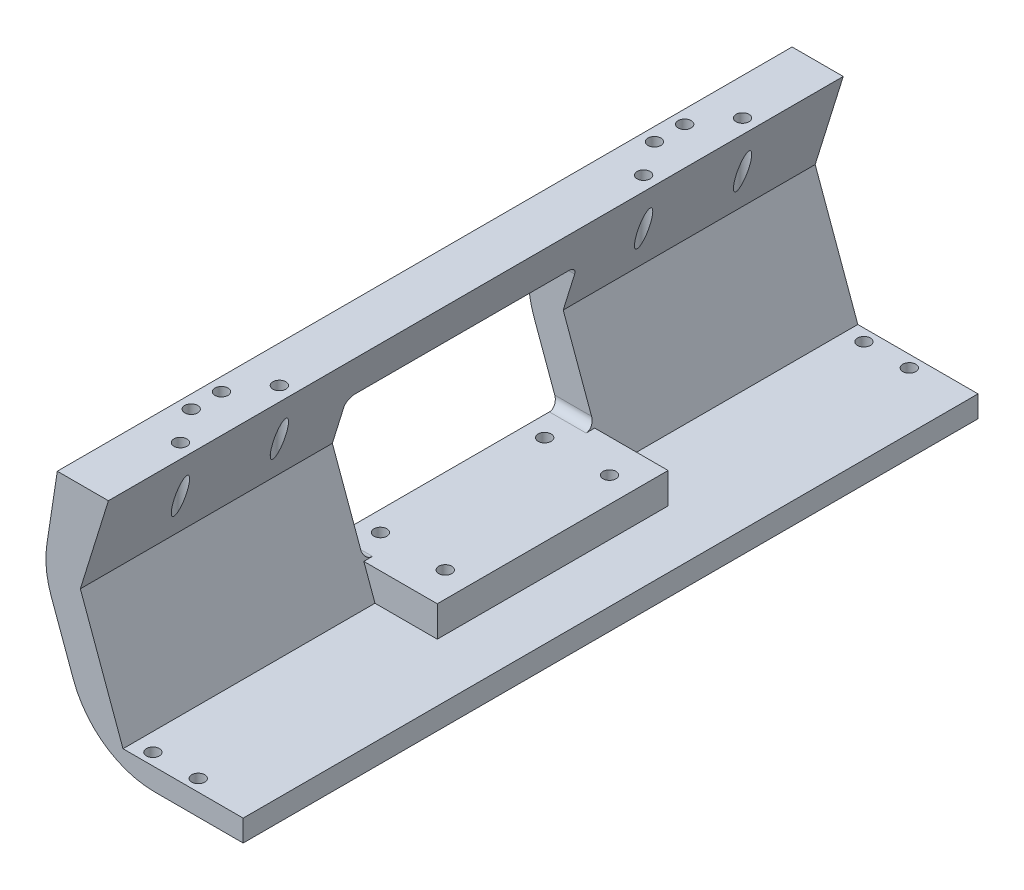
SolidWorks part; units mm, degrees
ref_plane "前视基准面" through (0, 0, 0) normal (0, 0, 1) x (1, 0, 0)
ref_plane "上视基准面" through (0, 0, 0) normal (0, 1, 0) x (1, 0, 0)
ref_plane "右视基准面" through (0, 0, 0) normal (1, 0, 0) x (0, 0, -1)
other "Configuration Table"
sketch "草图1" plane through (0, 0, 0) normal (0, 1, 0) x (1, 0, 0)
  line L0 (77.9817, 90) -> (77.9817, -80)
  line L1 (77.9817, 90) -> (105.7807, 90)
  line L3 (77.9817, -80) -> (105.7807, -80)
  line L4 (105.7807, 90) -> (105.7807, -80)
  circle A0 centre (82.1409, 87.25) radius 1.5
  circle A1 centre (92.6409, 87.25) radius 1.5
  circle A2 centre (82.1409, -77.25) radius 1.5
  circle A3 centre (92.6409, -77.25) radius 1.5
  point P0 (0, 0)
extrude "凸台-拉伸1" add sketch "草图1" along normal blind 5
sketch "草图2" plane through (0, 0, 80) normal (0, 0, 1) x (1, 0, 0)
  line L0 (70.1541, 3.1157) -> (59.6018, 32.1079)
  line L1 (77.9817, 5) -> (68.1152, 32.1079)
  line L2 (77.9817, 5) -> (105.7807, 5) construction
  line L3 (77.9817, 5) -> (63.6209, 44.4558) construction
  line L4 (70.4641, 2.2638) -> (56.1034, 41.7197) construction
  line L5 (70.1541, 3.1157) -> (71.2881, 0)
  line L6 (71.2881, 0) -> (77.9817, 0)
  line L7 (62.7747, 53) -> (74.6027, 53)
  line L9 (77.9817, 5) -> (77.9817, 0)
  line L13 (59.6018, 32.1079) -> (60.4325, 37.5776)
  line L14 (68.1152, 32.1079) -> (74.6027, 53)
  line L17 (62.7721, 53) -> (251.9817, 53) construction
  line L18 (60.4325, 37.5776) -> (62.7747, 53)
  dimension "D1" = 8
  dimension "D2" = 110
extrude "凸台-拉伸2" add sketch "草图2" against normal up to surface (170 mm away) up to face at (91.8812, 2.5, -90)
ref_plane "中间面" through (0, 0, -5) normal (0, 0, -1) x (-1, 0, 0)
fillet "圆角1" radius 20 1 edges at (59.6018, 32.1079, -5)
fillet "圆角2" radius 20 1 edges at (71.2881, 0, -5)
sketch "草图3" plane through (0, 53, 0) normal (0, 1, 0) x (1, 0, 0)
  circle A0 centre (71.2881, 70.0248) radius 1.5
  circle A1 centre (65.8418, 62.079) radius 1.5
  circle A2 centre (65.8418, 55.079) radius 1.5
  circle A3 centre (71.2881, 47.1331) radius 1.5
  circle A4 centre (71.2881, -37.1331) radius 1.5
  circle A5 centre (65.8418, -45.079) radius 1.5
  circle A6 centre (65.8418, -52.079) radius 1.5
  circle A7 centre (71.2881, -60.0248) radius 1.5
extrude "切除-拉伸1" cut sketch "草图3" against normal blind 22
sketch "草图5" plane through (0, 0, 0) normal (1, 0, 0) x (0, 0, -1)
  line L0 (5, 53) -> (5, -16.1066) construction
  line L1 (90, 53) -> (-80, 53) construction
  line L2 (5, -25.1016) -> (5, 25.1016) construction
  line L4 (-21.7056, 42.6301) -> (31.7056, 42.6301)
  line L5 (-21.7056, 42.6301) -> (-21.7056, 12.0981)
  line L6 (-21.7056, 12.0981) -> (31.7056, 12.0981)
  line L7 (31.7056, 42.6301) -> (31.7056, 12.0981)
extrude "切除-拉伸2" cut sketch "草图5" along normal blind 138
sketch "草图6" plane through (0, 5, 0) normal (0, 1, 0) x (1, 0, 0)
  line L0 (75.3982, 31.7056) -> (92.3883, 31.7056)
  line L2 (92.3883, 31.7056) -> (92.3883, -21.7056)
  line L3 (92.3883, -21.7056) -> (75.3982, -21.7056)
  line L4 (75.3982, -21.7056) -> (75.3982, 31.7056)
  line L5 (75.3982, 31.7056) -> (75.3982, -21.7056) construction
  point P2 (75.3982, -21.7056)
  point P5 (0, 0)
extrude "凸台-拉伸3" add sketch "草图6" along normal up to surface (7.0981 mm away) up to face at (71.1588, 12.0981, -5)
fillet "圆角3" radius 2 4 edges at (71.1588, 12.0981, -31.7056) (71.1588, 12.0981, 21.7056) (66.2912, 42.6301, 21.7056) (66.2912, 42.6301, -31.7056)
sketch "草图7" plane through (0, 12.0981, 0) normal (0, 1, 0) x (1, 0, 0)
  line L0 (71.5304, -14) -> (86.5304, -14) construction
  line L1 (86.5304, -14) -> (86.5304, 24) construction
  line L2 (86.5304, 24) -> (71.5304, 24) construction
  line L3 (71.5304, 24) -> (71.5304, -14) construction
  line L4 (92.3883, 5) -> (50092.3883, 5) construction
  line L5 (92.3883, -21.7056) -> (92.3883, 31.7056) construction
  circle A0 centre (71.5304, -14) radius 1.5
  circle A1 centre (71.5304, 24) radius 1.5
  circle A2 centre (86.5304, 24) radius 1.5
  circle A3 centre (86.5304, -14) radius 1.5
  point P12 (92.3883, 5)
  point P13 (0, 0)
  dimension "D3" = 3
  dimension "D1" = 38
  dimension "D2" = 15
extrude "切除-拉伸3" cut sketch "草图7" against normal blind 20
